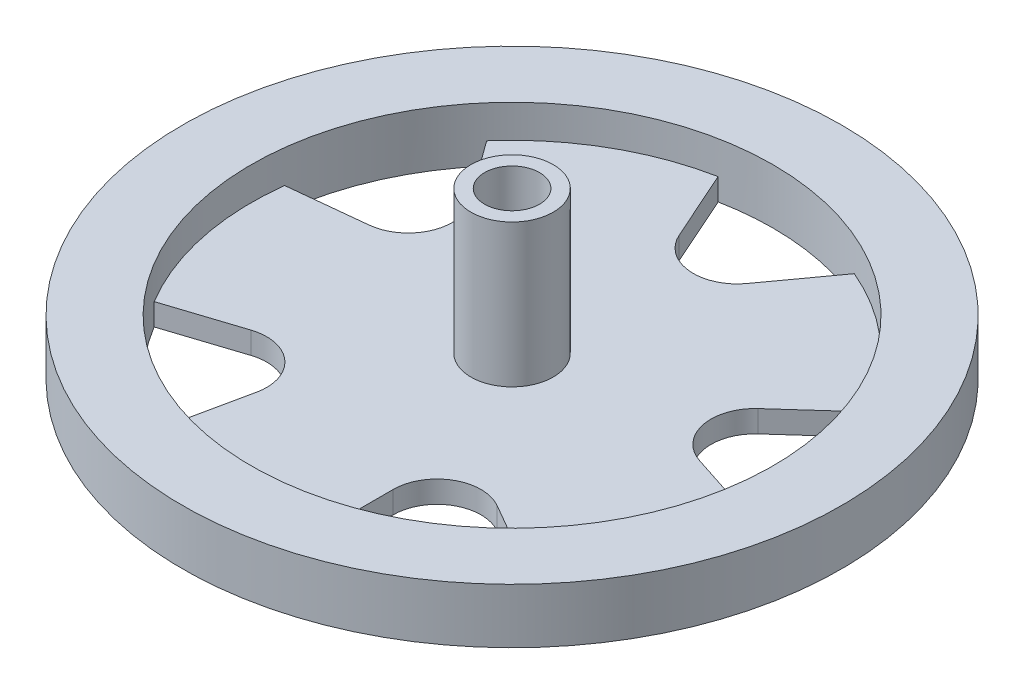
SolidWorks part; units mm, degrees
ref_plane "Front Plane" through (0, 0, 0) normal (0, 0, 1) x (1, 0, 0)
ref_plane "Top Plane" through (0, 0, 0) normal (0, 1, 0) x (1, 0, 0)
ref_plane "Right Plane" through (0, 0, 0) normal (1, 0, 0) x (0, 0, -1)
sketch "Sketch1" plane through (0, 0, 0) normal (0, 0, 1) x (1, 0, 0)
  line L0 (38.1, 6.35) -> (38.1, 0)
  line L1 (55, 0) -> (-55, 0) construction
  line L2 (38.1, 0) -> (0, 0)
  line L3 (0, 0) -> (0, 6.35)
  line L4 (0, -55) -> (0, 55) construction
  line L5 (0, 6.35) -> (3.175, 6.35)
  line L6 (3.175, 6.35) -> (3.175, 19.05)
  line L7 (3.175, 19.05) -> (4.7625, 19.05)
  line L8 (4.7625, 19.05) -> (4.7625, 2.54)
  line L9 (4.7625, 2.54) -> (30.1625, 2.54)
  line L10 (30.1625, 2.54) -> (30.1625, 6.35)
  line L11 (30.1625, 6.35) -> (38.1, 6.35)
  point P16 (3.9688, 19.05)
  dimension "D1" = 38.1
  dimension "D2" = 25.4
  dimension "D3" = 6.35
  dimension "D4" = 19.05
  dimension "D5" = 4.7625
  dimension "D6" = 3.175
  dimension "D7" = 12.7
  dimension "D8" = 2.54
revolve "Revolve1" add sketch "Sketch1" angle 360 about L3
ref_axis "Axis1" through (0, -1.4287, 0) along (0, 1, 0)
sketch "Sketch2" plane through (0, 0, 0) normal (0, -1, 0) x (1, 0, 0)
  line L0 (6.7588, 29.3955) -> (6.7588, 20.5055)
  line L1 (22.0778, 20.5511) -> (14.3788, 16.1061)
  arc A0 (6.7588, 29.3955) -> (22.0778, 20.5511) centre (0, 0) cw
  circle A1 centre (0, 0) radius 30.1625 construction
  circle A2 centre (0, 0) radius 30.1625 construction
  arc A3 (6.7588, 20.5055) -> (14.3788, 16.1061) centre (11.8388, 20.5055) ccw
  dimension "D3" = 5.08
  dimension "D1" = 60
  dimension "D2" = 8.89
extrude "Cut-Extrude1" cut sketch "Sketch2" against normal through all contours A3 L1 A0 L0
pattern_circular "CirPattern1" count 5 over 360 about axis through (0, -1.4287, 0) along (0, 1, 0) of "Cut-Extrude1"
sketch "Sketch4" plane through (0, 0, 0) normal (0, -1, 0) x (1, 0, 0)
  circle A0 centre (0, 0) radius 22.225
  dimension "D1" = 44.45
split line "Split Line1"
